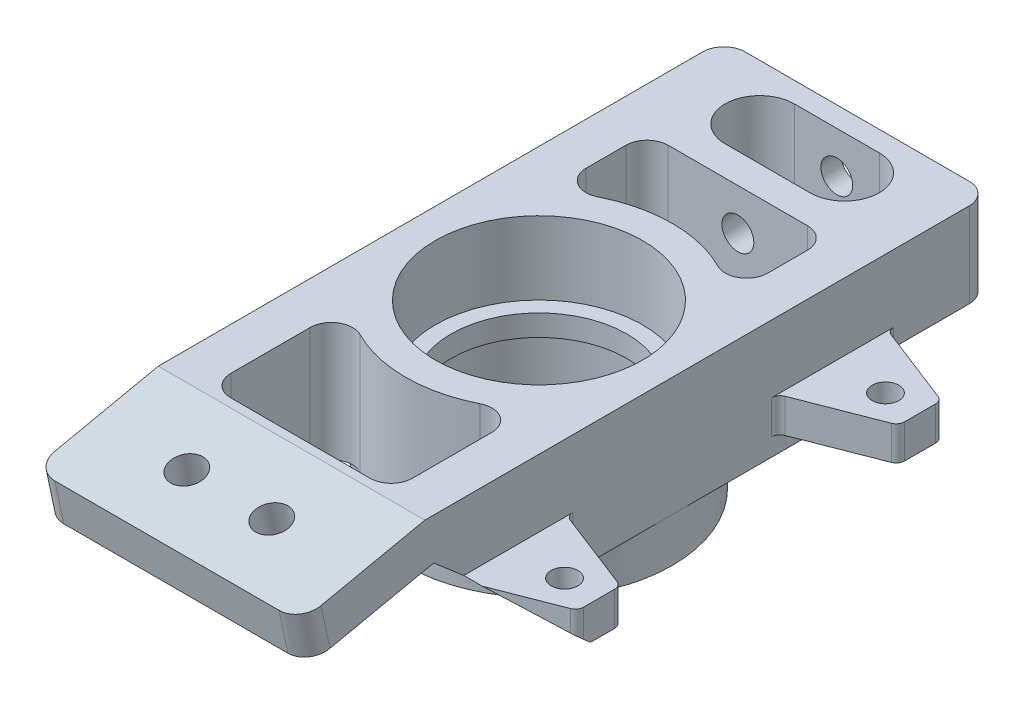
SolidWorks part; units mm, degrees
material "6061-T6 (SS)"
ref_plane "Front Plane" through (0, 0, 0) normal (0, 0, 1) x (1, 0, 0)
ref_plane "Top Plane" through (0, 0, 0) normal (0, 1, 0) x (1, 0, 0)
ref_plane "Right Plane" through (0, 0, 0) normal (1, 0, 0) x (0, 0, -1)
sketch "Geometry" plane through (0, 0, 0) normal (1, 0, 0) x (0, 0, -1)
  line L0 (0, 0) -> (0, -97.4059) construction
  line L1 (0, 0) -> (-30.7529, 0) construction
  line L2 (0, 22) -> (-45.5659, 22) construction
  dimension "D1" = 22
sketch "Sketch1" plane through (0, 0, 0) normal (0, 0, 1) x (1, 0, 0)
  line L1 (0, 0) -> (0, -13.28) construction
  line L3 (-30.9994, -10.5425) -> (-30.9994, -32.3865)
  line L4 (-30.9994, -32.3865) -> (-26.289, -32.3865)
  line L5 (-26.289, -32.3865) -> (-26.289, -38.7365)
  line L6 (-26.289, -38.7365) -> (-30.9994, -38.7365)
  line L7 (-30.9994, -38.7365) -> (-30.9994, -63.1205)
  line L8 (-30.9994, -63.1205) -> (-32.258, -63.1205)
  line L9 (-32.258, -63.1205) -> (-32.258, -59.3105)
  line L10 (-32.258, -59.3105) -> (-39.878, -59.3105)
  line L11 (-39.878, -59.3105) -> (-39.878, -10.5425)
  line L12 (-39.878, -10.5425) -> (-30.9994, -10.5425)
  line L13 (-80.1186, -10.5425) -> (80.1186, -10.5425) construction
  dimension "D1" = 6.35
  dimension "D2" = 21.844
  dimension "D3" = 24.384
  dimension "D4" = 52.578
  dimension "D5" = 61.9989
  dimension "D6" = 64.516
  dimension "D7" = 79.756
  dimension "D8" = 48.768
revolve "Bearing Housing" add sketch "Sketch1" angle 360 about L1
fillet "Bearing Fillet" radius 6.35 1 edges at (-32.258, -59.3105, 0)
sketch "Sketch2" plane through (0, -10.5425, 0) normal (0, -1, 0) x (-1, 0, 0)
  line L0 (-39.878, 50.8) -> (-39.878, 0)
  line L1 (39.878, 50.8) -> (39.878, 0)
  line L2 (-39.878, 50.8) -> (39.878, 50.8)
  circle A0 centre (0, 0) radius 39.878 construction
  arc A1 (-39.878, 0) -> (39.878, 0) centre (0, 0) cw
  dimension "D1" = 50.8
extrude "LBJ Prep" add sketch "Sketch2" along normal blind 35.56
sketch "Sketch3" plane through (-39.878, 0, 0) normal (-1, 0, 0) x (0, 0, 1)
  line L0 (-50.8, -10.5425) -> (-95.1865, -10.5425)
  line L1 (-95.1865, -10.5425) -> (-95.1865, -35.9425)
  line L2 (-95.1865, -35.9425) -> (-58.42, -35.9425)
  line L3 (-58.42, -35.9425) -> (-50.8, -46.1025)
  line L4 (-50.8, -46.1025) -> (-50.8, -10.5425)
  circle A1 centre (-78.74, -23.2425) radius 10.3505 construction
  dimension "D3" = 25.4
  dimension "D4" = 20.701
  dimension "D2" = 7.62
  dimension "D1" = 78.74
  dimension "D5" = 12.7
  dimension "D6" = 6.096
extrude "LBJ Extrude" add sketch "Sketch3" against normal up to surface (79.756 mm away) up to face at (39.878, -28.3225, -25.4)
sketch "Sketch4" plane through (0, -35.9425, 0) normal (0, -1, 0) x (1, 0, 0)
  line L0 (-12.7, -78.74) -> (12.7, -78.74) construction
  line L1 (0, -200000) -> (0, 200052.2037) construction
  line L2 (-12.7, -68.3895) -> (12.7, -68.3895)
  line L3 (-12.7, -89.0905) -> (12.7, -89.0905)
  arc A0 (-12.7, -68.3895) -> (-12.7, -89.0905) centre (-12.7, -78.74) ccw
  arc A1 (12.7, -89.0905) -> (12.7, -68.3895) centre (12.7, -78.74) ccw
  point P4 (0, -78.74)
  dimension "D1" = 20.701
  dimension "D2" = 78.74
  dimension "D3" = 25.4
extrude "LBJ Slot" cut sketch "Sketch4" against normal through all
sketch "Sketch8" plane through (0, -46.1025, 0) normal (0, -1, 0) x (1, 0, 0)
  line L0 (-27.178, -29.1824) -> (-27.178, -59.4995)
  line L1 (-27.178, -59.4995) -> (27.178, -59.4995)
  line L2 (27.178, -59.4995) -> (27.178, -29.1824)
  line L3 (-39.878, 0) -> (-39.878, -50.8) construction
  line L4 (39.878, -50.8) -> (39.878, 0) construction
  line L5 (12.7, -68.3895) -> (-12.7, -68.3895) construction
  arc A0 (-39.878, 0) -> (39.878, 0) centre (0, 0) ccw construction
  arc A1 (-27.178, -29.1824) -> (27.178, -29.1824) centre (0, 0) ccw
  dimension "D1" = 12.7
  dimension "D2" = 12.7
  dimension "D3" = 8.89
extrude "LBJ Weight Saivng" cut sketch "Sketch8" against normal up to surface (35.56 mm away) up to face at (0, -10.5425, -78.74)
fillet "LBJ Fillet" radius 6.35 4 edges at (-27.178, -23.2425, -59.4995) (27.178, -23.2425, -59.4995) (27.178, -28.3225, -29.1824) (-27.178, -28.3225, -29.1824)
sketch "Sketch12" plane through (0, 0, -95.1865) normal (0, 0, -1) x (-1, 0, 0)
  line L0 (0, 200000) -> (0, -200097.4059) construction
  circle A0 centre (0, -22.958) radius 4.7625
  dimension "D1" = 9.525
  dimension "D2" = 22.958
extrude "LBJ Hole" cut sketch "Sketch12" against normal up to surface (35.687 mm away) up to face at (0, -23.2425, -59.4995)
sketch "Alignment for LBJ Clearance" plane through (0, 0, -95.1865) normal (0, 0, -1) x (-1, 0, 0)
  line L0 (0, -22.958) -> (8.6177, -33.2282) construction
  line L1 (0, 200000) -> (0, -200097.4059) construction
  circle A1 centre (0, -22.958) radius 12.7 construction
  circle A2 centre (0, -22.958) radius 4.7625 construction
  dimension "D1" = 25.4
  dimension "D2" = 40
ref_plane "Plane1" through (0, -22.958, -95.1865) normal (-0.6428, -0.766, 0) x (-0.766, 0.6428, 0)
sketch "Sketch17" plane through (0, -22.958, -95.1865) normal (-0.6428, -0.766, 0) x (-0.766, 0.6428, 0)
  line L0 (0, -6.096) -> (0, -26.797) construction
  line L1 (4.7625, -26.797) -> (-4.7625, -26.797) construction
  line L3 (-4.7625, -6.096) -> (4.7625, -6.096) construction
  line L7 (4.7625, -26.797) -> (-4.7625, -26.797) construction
  line L8 (-1.27, -16.4465) -> (1.27, -16.4465) construction
  line L9 (-1.27, -6.096) -> (1.27, -6.096)
  line L10 (-1.27, -26.797) -> (1.27, -26.797)
  arc A2 (-1.27, -6.096) -> (-1.27, -26.797) centre (-1.27, -16.4465) ccw
  arc A3 (1.27, -26.797) -> (1.27, -6.096) centre (1.27, -16.4465) ccw
  point P7 (0, -16.4465)
  dimension "D1" = 2.54
  dimension "D2" = 20.701
extrude "LBJ Widening" cut sketch "Sketch17" along normal through all
mirror "LBJ Widening " about plane through (0, 0, 0) normal (1, 0, 0) of "LBJ Widening"
sketch "Sketch5" plane through (0, -10.5425, 0) normal (0, -1, 0) x (-1, 0, 0)
  line L0 (-39.878, -44.45) -> (39.878, -44.45)
  line L1 (39.878, -44.45) -> (39.878, 0)
  line L2 (-39.878, -44.45) -> (-39.878, 0)
  circle A0 centre (0, 0) radius 39.878 construction
  arc A1 (-39.878, 0) -> (39.878, 0) centre (0, 0) ccw
  dimension "D1" = 44.45
extrude "UBJ Area Prep" add sketch "Sketch5" along normal blind 35.56
sketch "UBJ Angle " plane through (-39.878, 0, 0) normal (-1, 0, 0) x (0, 0, 1)
  line L0 (44.45, -10.5425) -> (73.9986, -10.5425)
  line L1 (73.9986, -10.5425) -> (111.266, -18.4639)
  line L2 (111.266, -18.4639) -> (108.6256, -30.8864)
  line L3 (108.6256, -30.8864) -> (71.3581, -22.965)
  line L4 (71.3581, -22.965) -> (44.45, -46.1025)
  line L5 (44.45, -46.1025) -> (44.45, -10.5425)
  line L6 (92.6323, -14.5032) -> (69.5361, -123.1622) construction
  line L7 (71.3581, -22.965) -> (73.9986, -10.5425) construction
  line L8 (0, 0) -> (79.4354, 0) construction
  line L9 (44.45, -10.5425) -> (-95.1865, -10.5425) construction
  line L10 (-27.2547, 22) -> (21.0785, 22) construction
  line L11 (0, 0) -> (0, 33.0044) construction
  circle A0 centre (84.7344, -51.66) radius 10.3251 construction
  dimension "D8" = 20.6502
  dimension "D1" = 19.05
  dimension "D2" = 38.1
  dimension "D3" = 12.7
  dimension "D5" = 22
  dimension "D7" = 12
  dimension "D4" = 84.7344
  dimension "D6" = 73.66
extrude "UBJ Angle Mount" add sketch "UBJ Angle " against normal up to surface (79.756 mm away) up to face at (39.878, -33.0396, -30.099)
sketch "Sketch7" plane through (0, -7.4603, -1.5857) normal (0, -0.9781, -0.2079) x (1, 0, 0)
  line L0 (0, 112.6735) -> (0, 78.6798) construction
  line L2 (-12.7, 93.6235) -> (12.7, 93.6235) construction
  line L3 (39.878, 112.6735) -> (-39.878, 112.6735) construction
  circle A2 centre (-12.7, 93.6235) radius 4.9022
  circle A3 centre (12.7, 93.6235) radius 4.9022
  point P3 (0, 93.6235)
  dimension "D3" = 9.8044
  dimension "D4" = 9.8044
  dimension "D1" = 25.4
  dimension "D2" = 19.05
extrude "Camber Block Holes" cut sketch "Sketch7" against normal up to surface (12.7 mm away) up to face at (0, -14.5032, 92.6323)
sketch "Sketch9" plane through (0, -46.1025, 0) normal (0, -1, 0) x (1, 0, 0)
  line L0 (-27.178, 29.1824) -> (-27.178, 71.3581)
  line L1 (-27.178, 71.3581) -> (27.178, 71.3581)
  line L2 (27.178, 71.3581) -> (27.178, 29.1824)
  line L4 (-39.878, 44.45) -> (-39.878, 0) construction
  line L5 (39.878, 0) -> (39.878, 44.45) construction
  line L6 (39.878, 71.3581) -> (-39.878, 71.3581) construction
  arc A3 (-27.178, 29.1824) -> (27.178, 29.1824) centre (0, 0) cw
  arc A4 (39.878, 0) -> (-39.878, 0) centre (0, 0) ccw construction
  dimension "D1" = 12.7
  dimension "D2" = 12.7
extrude "UBJ Weight Saving" cut sketch "Sketch9" against normal up to surface (35.56 mm away) up to face at (-30.9994, -10.5425, 0)
fillet "UBJ Fillets" radius 6.35 4 edges at (27.178, -28.3225, 29.1824) (-27.178, -28.3225, 29.1824) (27.178, -16.7537, 71.3581) (-27.178, -16.7537, 71.3581)
ref_plane "Brake Caliper Face " through (0, -30.7025, 0) normal (0, 1, 0) x (1, 0, 0)
sketch "Sketch13" plane through (0, -30.7025, 0) normal (0, 1, 0) x (1, 0, 0)
  line L0 (55.6468, 116.3651) -> (55.6468, 49.0638) construction
  line L1 (0, 0) -> (78.791, 0) construction
  line L2 (65.9968, -54.35) -> (65.9968, -41.65)
  line L3 (65.9968, -41.65) -> (39.878, -31.49)
  line L4 (39.878, -31.49) -> (39.878, -64.51)
  line L5 (39.878, -64.51) -> (65.9968, -54.35)
  line L6 (39.878, 95.1865) -> (39.878, -73.9986) construction
  line L7 (65.9968, -48) -> (55.6468, -48) construction
  line L8 (39.878, 31.49) -> (39.878, 64.51)
  line L9 (39.878, 64.51) -> (65.9968, 54.35)
  line L10 (65.9968, 54.35) -> (65.9968, 41.65)
  line L11 (65.9968, 41.65) -> (39.878, 31.49)
  circle A0 centre (55.6468, -48) radius 4
  circle A1 centre (55.6468, 48) radius 4
  dimension "D3" = 8
  dimension "D1" = 55.6468
  dimension "D2" = 96
  dimension "D4" = 6.35
  dimension "D5" = 33.02
  dimension "D6" = 12.7
extrude "Brake Arms" add sketch "Sketch13" against normal blind 10.16
sketch "Sketch15" plane through (39.878, 0, 0) normal (-1, 0, 0) x (0, 0, 1)
  line L0 (64.51, -28.8535) -> (50.5439, -40.8625)
  line L1 (44.45, -46.1025) -> (71.3581, -22.965) construction
  line L2 (50.5439, -40.8625) -> (64.51, -40.8625)
  line L3 (50.5439, -40.8625) -> (64.51, -40.8625) construction
  line L4 (64.51, -28.8535) -> (64.51, -40.8625)
  line L5 (64.51, -40.8625) -> (64.51, -30.7025) construction
extrude "Upper Brake Cut" cut sketch "Sketch15" against normal through all
sketch "Sketch16" plane through (39.878, 0, 0) normal (-1, 0, 0) x (0, 0, 1)
  line L0 (-58.42, -35.9425) -> (-95.1865, -35.9425)
  line L1 (-95.1865, -35.9425) -> (-58.42, -35.9425) construction
  line L2 (-95.1865, -35.9425) -> (-95.1865, -46.1025)
  line L3 (-95.1865, -46.1025) -> (-50.8, -46.1025)
  line L4 (-50.8, -46.1025) -> (-58.42, -35.9425)
  line L5 (-95.1865, -10.5425) -> (-95.1865, -35.9425) construction
extrude "Lower Brake Cut" cut sketch "Sketch16" against normal through all
fillet "Fillet1" radius 2.54 7 edges at (65.9968, -34.1461, 54.35) (65.9968, -35.7825, 41.65) (65.9968, -35.7825, -41.65) (65.9968, -35.7825, -54.35) (39.878, -33.3225, -64.51) (39.878, -35.7825, -31.49) (39.878, -35.7825, 31.49)
sketch "Sketch14" plane through (-39.878, 0, 0) normal (-1, 0, 0) x (0, 0, 1)
  line L0 (73.9986, -10.5425) -> (-95.1865, -10.5425) construction
  circle A0 centre (-31.242, -20.1945) radius 1.27
  circle A1 centre (-31.242, -37.4665) radius 1.27
  circle A2 centre (-55.118, -20.1945) radius 1.27
  dimension "D3" = 2.54
  dimension "D4" = 2.54
  dimension "D5" = 2.54
  dimension "D1" = 17.272
  dimension "D2" = 23.876
  dimension "D6" = 31.242
  dimension "D7" = 9.652
extrude "Tie Rod Mound" cut sketch "Sketch14" against normal blind 6.35
fillet "Fillet2" radius 6.35 4 edges at (-39.878, -23.2425, -95.1865) (39.878, -23.2425, -95.1865) (39.878, -24.6752, 109.9458) (-39.878, -24.6752, 109.9458)
equation "\"Wheel_Offset\"= 22mm"
equation "\"HUB_to_UBJ_Lat\"= 2.9in"
equation "\"Hub_to_UBJ_Vert\"= 3.336in"
equation "\"Hub_to_LBJ_Lat\"= 1.77in"
equation "\"Hub_to_LBJ_Vert\"= 3.1in"
equation "\"Wheel_face_to_Upright_back\"= 1.2812in'This is the distance between the whee face to the upright back."
equation "\"D2@Sketch4\"=\"Hub_to_LBJ_Vert\""
equation "\"D5@UBJ Angle \" = \"Wheel_Offset\""
equation "\"UBJ_Angle\"= 12deg"
equation "\"D7@UBJ Angle \" = \"UBJ_Angle\""
equation "\"D4@UBJ Angle \"=\"Hub_to_UBJ_Vert\""
equation "\"D6@UBJ Angle \"=\"HUB_to_UBJ_Lat\""
equation "\"D1@Geometry\" = \"Wheel_Offset\""
equation "\"D2@Sketch12\"=\"Hub_to_LBJ_Lat\"-\"Wheel_Offset\""
equation "\"D1@Sketch3\"=\"Hub_to_LBJ_Vert\""
equation "\"D1@Sketch7\"=\"Hub_to_LBJ_Lat\""
